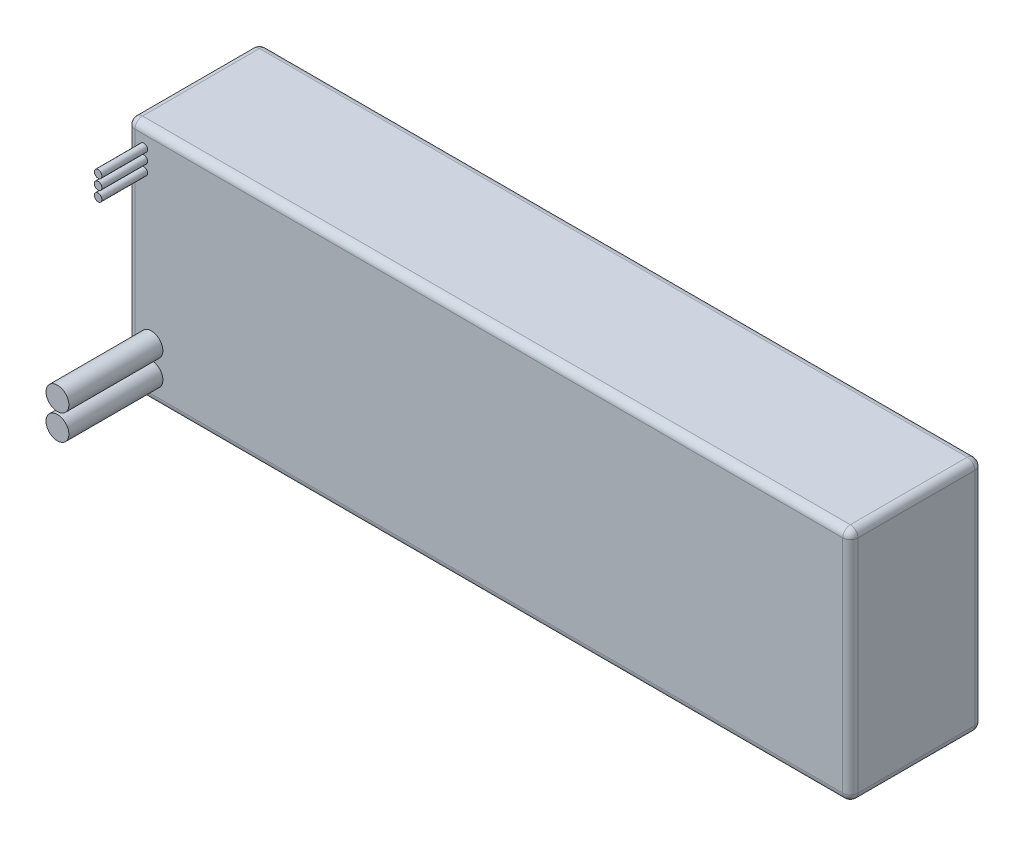
SolidWorks part; units mm, degrees
ref_plane "Front Plane" through (0, 0, 0) normal (0, 0, 1) x (1, 0, 0)
ref_plane "Top Plane" through (0, 0, 0) normal (0, 1, 0) x (1, 0, 0)
ref_plane "Right Plane" through (0, 0, 0) normal (1, 0, 0) x (0, 0, -1)
sketch "Sketch1" plane through (0, 0, 0) normal (0, 0, 1) x (1, 0, 0)
  line L1 (-71.15, -23.25) -> (71.15, -23.25)
  line L2 (-71.15, -23.25) -> (-71.15, 23.25)
  line L3 (-71.15, 23.25) -> (71.15, 23.25)
  line L4 (71.15, -23.25) -> (71.15, 23.25)
  dimension "D1" = 142.3
  dimension "D2" = 71.15
  dimension "D3" = 46.5
  dimension "D4" = 23.25
extrude "Boss-Extrude1" add sketch "Sketch1" along normal blind 13 and the other way blind 13
fillet "Fillet1" radius 1.5 12 edges at (-71.15, 0, -13) (0, -23.25, -13) (-71.15, -23.25, 0) (71.15, 0, -13) (71.15, -23.25, 0) (0, 23.25, -13) (71.15, 23.25, 0) (-71.15, 23.25, 0) (0, 23.25, 13) (71.15, 0, 13) (0, -23.25, 13) (-71.15, 0, 13)
sketch "Sketch2" plane through (0, 0, 13) normal (0, 0, 1) x (1, 0, 0)
  line L0 (69.65, -23.25) -> (-69.65, -23.25) construction
  line L1 (-71.15, -21.75) -> (-71.15, 21.75) construction
  circle A0 centre (-66.4, -18.25) radius 2.25
  circle A1 centre (-66.4, -13.25) radius 2.25
  point P6 (0, 0)
  dimension "D1" = 4.5
  dimension "D3" = 4.5
  dimension "D5" = 7
  dimension "D2" = 5
  dimension "D4" = 5
extrude "Boss-Extrude2" add sketch "Sketch2" along normal blind 18.5
sketch "Sketch3" plane through (0, 0, 13) normal (0, 0, 1) x (1, 0, 0)
  line L1 (-69.65, 23.25) -> (69.65, 23.25) construction
  line L2 (-71.15, -21.75) -> (-71.15, 21.75) construction
  circle A0 centre (-67.9, 19.5) radius 0.75
  circle A1 centre (-67.9, 17.5) radius 0.75
  circle A2 centre (-67.9, 15.5) radius 0.75
  point P8 (0, 0)
  point P9 (0, 0)
  point P10 (0, 0)
  dimension "D1" = 1.5
  dimension "D2" = 8.5
  dimension "D3" = 4
  dimension "D4" = 1.5
  dimension "D5" = 1.5
  dimension "D6" = 2
  dimension "D7" = 2
extrude "Boss-Extrude3" add sketch "Sketch3" along normal blind 9
